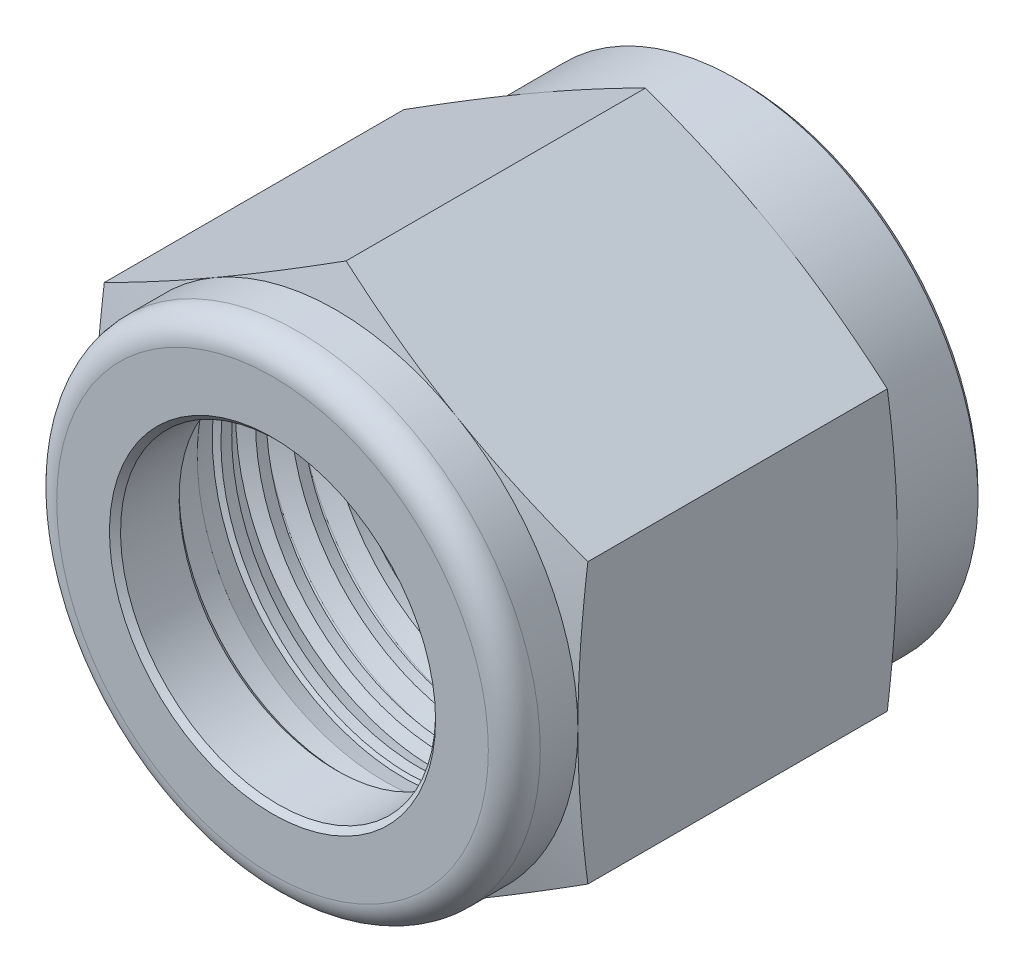
SolidWorks part; units mm, degrees
ref_plane "Front Plane" through (0, 0, 0) normal (0, 0, 1) x (1, 0, 0)
ref_plane "Top Plane" through (0, 0, 0) normal (0, 1, 0) x (1, 0, 0)
ref_plane "Right Plane" through (0, 0, 0) normal (1, 0, 0) x (0, 0, -1)
sketch "Sketch0" plane through (0, 0, 0) normal (1, 0, 0) x (0, 0, -1)
  line L0 (0, 0) -> (-21.5646, 0) construction
  line L4 (-21.5646, 11.1125) -> (-21.5646, -11.1125) construction
  line L5 (-21.5646, 11.1125) -> (-21.5646, -11.1125) construction
  line L6 (-21.5646, 7.239) -> (-21.5646, -7.239) construction
  line L7 (0, 9.525) -> (0, -9.525) construction
  line L8 (0, -9.525) -> (0, 9.525) construction
  line L9 (0, -9.525) -> (-1.5875, -9.525) construction
  point P16 (-18.3642, 0)
  point P20 (-16.4338, 0)
  point P22 (-12.2936, 0)
  point P34 (-3.9624, 0)
  point P35 (-18.6436, 0)
  dimension "P" = 22.225
  dimension "M" = 21.5646
  dimension "L" = 18.3642
  dimension "S" = 16.4338
  dimension "Q" = 12.2936
  dimension "A" = 14.478
  dimension "C" = 22.225
  dimension "T" = 19.05
  dimension "B" = 3.9624
  dimension "J" = 14.6812
  dimension "H" = 19.05
  dimension "Pitch" = 1.5875
sketch "Sketch1" plane through (0, 0, 0) normal (0, 0, 1) x (1, 0, 0)
  line L1 (0, 12.8316) -> (-11.1125, 6.4158)
  line L2 (-11.1125, 6.4158) -> (-11.1125, -6.4158)
  line L3 (-11.1125, -6.4158) -> (0, -12.8316)
  line L4 (0, -12.8316) -> (11.1125, -6.4158)
  line L5 (11.1125, -6.4158) -> (11.1125, 6.4158)
  line L6 (11.1125, 6.4158) -> (0, 12.8316)
  circle A0 centre (0, 0) radius 11.1125 construction
extrude "Boss-Extrude1" add sketch "Sketch1" along normal up to vertex (21.5646 mm away) up to point (0, 0, 21.5646)
sketch "Sketch2" plane through (0, 0, 0) normal (1, 0, 0) x (0, 0, -1)
  line L0 (-21.5646, 14.5507) -> (-21.5646, 11.1125)
  line L1 (-21.5646, 11.1125) -> (-18.6436, 11.1125)
  line L2 (-18.6436, 11.1125) -> (-18.183, 12.8316)
  line L3 (-21.5646, 12.8316) -> (0, 12.8316) construction
  line L4 (-18.183, 12.8316) -> (-4.423, 12.8316)
  line L5 (-4.423, 12.8316) -> (-3.9624, 11.1125)
  line L6 (-3.9624, 11.1125) -> (-18.6436, 11.1125) construction
  line L7 (-3.9624, 11.1125) -> (0, 11.1125)
  line L8 (0, 11.1125) -> (0, 14.5507)
  line L9 (-21.5646, 14.5507) -> (0, 14.5507)
  line L10 (-3.9624, 11.1125) -> (-3.9624, 0) construction
  line L11 (-18.6436, 11.1125) -> (-18.6436, 0) construction
  line L12 (-21.5646, 7.239) -> (-21.5646, 0)
  line L13 (-21.5646, 11.1125) -> (-21.5646, -11.1125) construction
  line L14 (-21.5646, 0) -> (0, 0)
  line L15 (0, 0) -> (0, 8.7517)
  line L16 (-18.3642, 7.239) -> (-18.3642, 0) construction
  line L17 (-18.3642, 7.239) -> (-18.3642, 8.4977)
  line L18 (-18.1102, 8.7517) -> (0, 8.7517)
  line L19 (-18.3642, 7.239) -> (-21.5646, 7.239)
  line L23 (-16.4338, 0) -> (-16.4338, 8.7517) construction
  arc A0 (-18.3642, 8.4977) -> (-18.1102, 8.7517) centre (-18.1102, 8.4977) cw
  dimension "D3" = 0.254
  dimension "D1" = 15
  dimension "D2" = 15
  dimension "D4" = 0.7733
revolve "Cut-Revolve1" cut sketch "Sketch2" angle 360 about L0
sketch "Sketch3" plane through (0, 0, 0) normal (0, 0, -1) x (-1, 0, 0)
  circle A0 centre (0, 0) radius 8.7517
  circle A1 centre (0, 0) radius 8.7517 construction
  point P3 (0, 8.7517)
fillet "Fillet1" radius 1.1938 1 edges at (11.1125, 0, 21.5646)
chamfer "Chamfer1" distance 0.254 angle 45 1 edges at (11.1125, 0, 0)
chamfer "Chamfer2" distance 0.254 angle 45 2 edges at (0, 7.239, 18.3642) (0, 7.239, 21.5646)
ref_axis "Centre Axis 1" through (0, 0, 25.2505) along (0, 0, -1)
curve "Helix/Spiral1" pitch 1.5875 height 18.0213 radius 8.7517 centre (0, 0, 0) axis (0, 0, 1) start towards (0, 1, 0) parameters "Pitch"=1.5875
sketch "Sketch4" plane through (0, 0, 0) normal (1, 0, 0) x (0, 0, -1)
  line L0 (-0.248, 8.322) -> (1.3395, 8.322) construction
  line L1 (1.3395, 8.322) -> (0.5457, 9.6969) construction
  line L2 (0.5457, 9.6969) -> (-0.248, 8.322) construction
  line L3 (0.4465, 9.525) -> (0.6449, 9.525) construction
  line L4 (0.5457, 8.7517) -> (0.5457, 8.322) construction
  line L5 (0, 8.7517) -> (1.0914, 8.7517) construction
  line L6 (0.5457, 9.6969) -> (0.5457, 9.525) construction
  line L7 (0.4465, 9.525) -> (-0.124, 8.5369)
  line L8 (-0.124, 8.5369) -> (1.2154, 8.5369)
  line L9 (1.2154, 8.5369) -> (0.6449, 9.525)
  arc A0 (0.6449, 9.525) -> (0.4465, 9.525) centre (0.5457, 9.4677) ccw
  point P6 (0.5457, 8.5369)
  dimension "D1" = 1.5875
  dimension "D2" = 1.3748
  dimension "D4" = 0.4296
  dimension "D3" = 0.1719
  dimension "D5" = 0.7733
sweep "Cut-Sweep1" cut profiles "Sketch4" path "Helix/Spiral1" align with end faces yes
sketch "Sketch5" plane through (0, 0, 0) normal (0, 0, -1) x (-1, 0, 0)
  circle A0 centre (0, 0) radius 9.525
extrude "Cut-Extrude1" cut sketch "Sketch5" against normal through all draft 45
sketch "Sketch6" plane through (0, 0, 0) normal (1, 0, 0) x (0, 0, -1)
  line L0 (-18.3642, 9.6969) -> (-12.2936, 9.6969)
  line L1 (-12.2936, 9.6969) -> (-16.4338, 8.7517)
  line L2 (-16.4338, 8.7517) -> (-18.3642, 8.7517)
  line L3 (-18.3642, 8.7517) -> (-18.3642, 9.6969)
  line L4 (-12.2936, 0) -> (-12.2936, 9.6969) construction
  line L5 (-16.4338, 0) -> (-16.4338, 8.7517) construction
  line L7 (-18.3642, 8.7517) -> (-18.3642, 0) construction
  line L8 (-18.1102, 8.7517) -> (0, 8.7517) construction
  line L9 (-12.2936, 9.6969) -> (0.5457, 9.6969) construction
revolve "Revolve1" add sketch "Sketch6" angle 360 about L0
sketch "SketchX" plane through (0, 0, 0) normal (0, 0, -1) x (-1, 0, 0)
  line L0 (0, 0) -> (-4.7625, 8.2489) construction
  line L1 (-5.5562, 9.6237) -> (-11.1125, 6.4158) construction
  circle A0 centre (0, 0) radius 9.525 construction
equation "\"D3@Helix/Spiral1\"= \"Pitch@Sketch0\" + \"S@Sketch0\""
equation "\"D1@Sketch4\"=\"Pitch@Sketch0\""
equation "\"Pitch@Helix/Spiral1\"=\"Pitch@Sketch0\""
